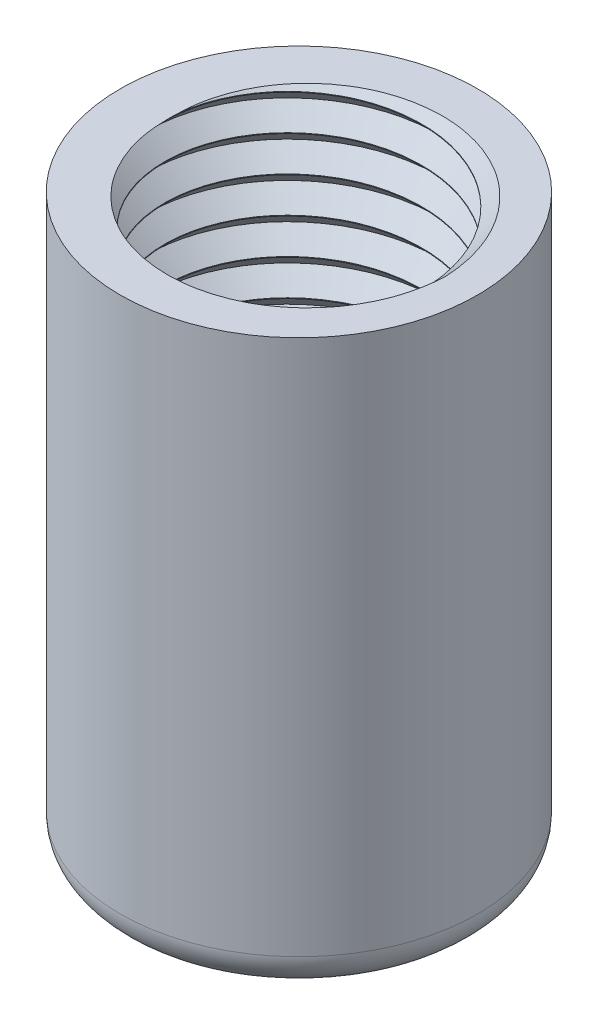
SolidWorks part; units mm, degrees
ref_plane "Plan de face" through (0, 0, 0) normal (0, 0, 1) x (1, 0, 0)
ref_plane "Plan de dessus" through (0, 0, 0) normal (0, 1, 0) x (1, 0, 0)
ref_plane "Plan de droite" through (0, 0, 0) normal (1, 0, 0) x (0, 0, -1)
sketch "Esquisse1" plane through (0, 0, 0) normal (0, 1, 0) x (1, 0, 0)
  circle A0 centre (0, 0) radius 25
  dimension "D1" = 50
extrude "Boss.-Extru.1" add sketch "Esquisse1" along normal blind 80 contours A0
shell "Coque1" thickness 7
sketch "Esquisse2" plane through (0, 80, 0) normal (0, 1, 0) x (1, 0, 0)
  circle A0 centre (0, 0) radius 20.5
  circle A1 centre (0, 0) radius 18 construction
  dimension "D1" = 2.5
curve "Hélice/Spirale1" pitch 5 height 50 turns 10
sketch "Esquisse3" plane through (0, 0, 0) normal (0, 0, 1) x (1, 0, 0)
  line L0 (18, 82.4495) -> (18, 77.5495)
  line L1 (18, 77.5495) -> (20.5, 80)
  line L2 (20.5, 80) -> (18, 82.4495)
  line L3 (18, 80) -> (-18, 80) construction
  line L4 (25, 80) -> (-25, 80) construction
  point P5 (0, 80)
  dimension "D1" = 4.9
  dimension "D2" = 2.5
  dimension "D3" = 3.5
  dimension "D4" = 0
  dimension "D5" = 18
sweep "Enlèvement de matière-Balayage1" cut profiles "Esquisse3" path "Hélice/Spirale1"
sketch "Esquisse4" plane through (0, 7, 0) normal (0, 1, 0) x (1, 0, 0)
  circle A0 centre (0, 0) radius 7.5
  dimension "D1" = 15
extrude "Enlèv. mat.-Extru.1" cut sketch "Esquisse4" against normal up to surface (7 mm away) up to face at (0, 0, 25)
fillet "Congé1" radius 5 1 edges at (0, 0, 25)
